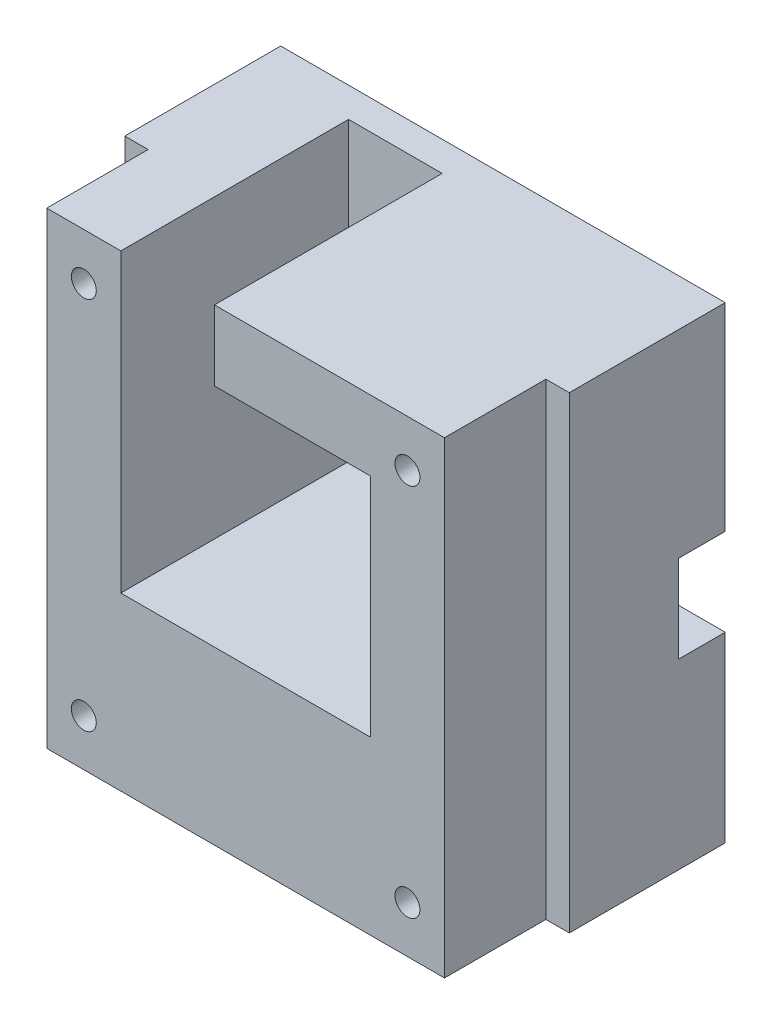
SolidWorks part; units mm, degrees
ref_plane "Front Plane" through (0, 0, 0) normal (0, 0, 1) x (1, 0, 0)
ref_plane "Top Plane" through (0, 0, 0) normal (0, 1, 0) x (1, 0, 0)
ref_plane "Right Plane" through (0, 0, 0) normal (1, 0, 0) x (0, 0, -1)
sketch "Sketch1" plane through (0, 0, 0) normal (0, 0, 1) x (1, 0, 0)
  line L1 (0, 0) -> (28.5, 0)
  line L2 (0, 0) -> (0, 30)
  line L3 (0, 30) -> (28.5, 30)
  line L4 (28.5, 0) -> (28.5, 30)
  dimension "D1" = 28.5
  dimension "D2" = 30
extrude "Boss-Extrude1" add sketch "Sketch1" along normal blind 16.5
sketch "Sketch2" plane through (0, 0, 16.5) normal (0, 0, 1) x (1, 0, 0)
  line L0 (0, 30) -> (0, 0) construction
  line L1 (12.25, 30) -> (12.25, 25.5)
  line L2 (12.25, 25.5) -> (22.25, 25.5)
  line L4 (6.25, 28.4669) -> (6.25, 11)
  line L6 (22.25, 25.5) -> (22.25, 11)
  line L7 (6.25, 28.4669) -> (6.25, 30)
  line L8 (28.5, 30) -> (0, 30) construction
  line L9 (6.25, 30) -> (12.25, 30)
  line L10 (6.25, 11) -> (22.25, 11)
  point P6 (0, 0)
  dimension "D1" = 16
  dimension "D2" = 14.5
  dimension "D3" = 6.25
  dimension "D4" = 6
  dimension "D5" = 4.5
extrude "Cut-Extrude1" cut sketch "Sketch2" against normal blind 14.6
sketch "Sketch3" plane through (0, 0, 1.9) normal (0, 0, 1) x (1, 0, 0)
  line L0 (6.25, 11) -> (22.25, 11) construction
  line L2 (22.25, 11) -> (22.25, 25.5) construction
  circle A0 centre (18.75, 14.5) radius 2.8
  dimension "D2" = 3.5
  dimension "D3" = 5.6
  dimension "D1" = 3.5
extrude "Cut-Extrude2" cut sketch "Sketch3" against normal through all
sketch "Sketch4" plane through (0, 0, 0) normal (0, 0, -1) x (-1, 0, 0)
  line L0 (-18.75, 17.3) -> (-28.5, 17.3)
  line L6 (-28.5, 0) -> (-28.5, 30) construction
  line L7 (-28.5, 17.3) -> (-28.5, 11.7)
  line L8 (-28.5, 11.7) -> (-18.75, 11.7)
  circle A2 centre (-18.75, 14.5) radius 2.8 construction
  arc A3 (-18.75, 11.7) -> (-18.75, 17.3) centre (-18.75, 14.5) cw
extrude "Cut-Extrude3" cut sketch "Sketch4" against normal blind 3
sketch "Sketch5" plane through (0, 0, 0) normal (0, 0, 1) x (1, 0, 0)
  line L0 (28.5, 30) -> (12.25, 30) construction
  line L1 (28.5, 0) -> (28.5, 30) construction
  line L2 (0, 15) -> (28.5, 15) construction
  line L3 (0, 30) -> (0, 0) construction
  line L4 (14.25, 0) -> (14.25, 30) construction
  line L5 (0, 0) -> (28.5, 0) construction
  line L8 (6.25, 30) -> (0, 30) construction
  circle A0 centre (24.625, 27) radius 0.8
  circle A1 centre (24.625, 3) radius 0.8
  circle A2 centre (3.875, 3) radius 0.8
  circle A3 centre (3.875, 27) radius 0.8
  point P14 (14.25, 15)
  point P17 (0, 0)
  point P24 (14.25, 15)
  point P26 (0, 0)
  point P27 (0, 0)
  dimension "D1" = 1.6
  dimension "D4" = 3
  dimension "D6" = 3
  dimension "D2" = 3
  dimension "D3" = 3.875
  dimension "D5" = 3.875
sketch "Sketch6" [suppressed] plane through (0, 0, 16.5) normal (0, 0, 1) x (1, 0, 0)
  line L0 (22.25, 25.5) -> (6.25, 11) construction
  line L1 (22.25, 11) -> (6.25, 25.5) construction
  line L2 (6.25, 30) -> (6.25, 11) construction
  circle A1 centre (14.25, 18.25) radius 2.8553
  point P9 (14.25, 18.25)
sketch "Sketch7" plane through (0, 0, 16.5) normal (0, 0, 1) x (1, 0, 0)
  line L0 (0, 0) -> (28.5, 0) construction
  line L1 (0, 30) -> (1.5, 30)
  line L2 (0, 30) -> (0, 0)
  line L3 (0, 0) -> (1.5, 0)
  line L4 (1.5, 30) -> (1.5, 0)
  line L6 (28.5, 30) -> (27, 30)
  line L7 (28.5, 30) -> (28.5, 0)
  line L8 (28.5, 0) -> (27, 0)
  line L9 (27, 30) -> (27, 0)
  dimension "D1" = 1.5
  dimension "D2" = 1.5
extrude "Cut-Extrude5" cut sketch "Sketch7" against normal blind 6.5
extrude "Cut-Extrude6" cut sketch "Sketch5" against normal blind 6.5 from surface starting at face at (13.85, 19.3, 16.5)
